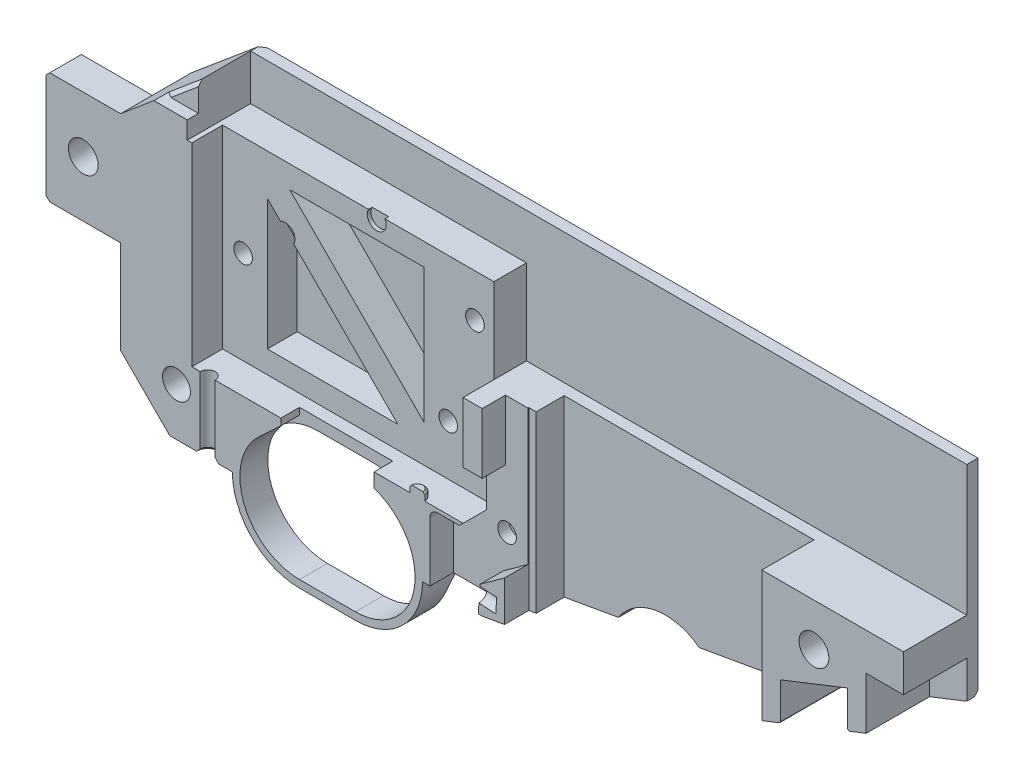
SolidWorks part; units mm, degrees
ref_plane "정면" through (0, 0, 0) normal (0, 0, 1) x (1, 0, 0)
ref_plane "윗면" through (0, 0, 0) normal (0, 1, 0) x (1, 0, 0)
ref_plane "우측면" through (0, 0, 0) normal (1, 0, 0) x (0, 0, -1)
sketch "스케치1" plane through (0, 0, 0) normal (0, 0, 1) x (1, 0, 0)
  line L0 (0, 0) -> (20, 0)
  line L1 (20, 0) -> (37.8763, 15)
  line L2 (37.8763, 15) -> (230, 15)
  line L3 (230, 15) -> (230, -54.9955)
  line L4 (230, -54.9955) -> (192, -54.9955)
  line L5 (0, 0) -> (0, -30)
  line L6 (0, -30) -> (20, -30)
  line L7 (20, -30) -> (20, -55)
  line L8 (20, -55) -> (33.22, -68.22)
  line L9 (33.22, -68.22) -> (50, -68.22)
  line L10 (68, -68.22) -> (83, -68.22) construction
  line L11 (68, -52.22) -> (83, -52.22)
  line L12 (68, -84.22) -> (83, -84.22)
  line L13 (67.2987, -49.22) -> (82.2987, -49.22)
  line L14 (139.5521, -64.2435) -> (117, -68.22)
  line L15 (101, -68.22) -> (117, -68.22)
  line L16 (117, -68.22) -> (192, -54.9955) construction
  line L17 (68, -86.22) -> (83, -86.22)
  line L18 (161.2179, -60.4232) -> (192, -54.9955)
  line L20 (68, -50.22) -> (83, -50.22) construction
  arc A0 (68, -52.22) -> (68, -84.22) centre (68, -68.22) ccw
  arc A1 (83, -84.22) -> (83, -52.22) centre (83, -68.22) ccw
  arc A3 (68, -50.22) -> (68, -86.22) centre (68, -68.22) ccw construction
  arc A4 (83, -86.22) -> (101, -68.22) centre (83, -68.22) ccw
  arc A5 (83, -86.22) -> (83, -50.22) centre (83, -68.22) ccw construction
  arc A6 (161.2179, -60.4232) -> (139.5521, -64.2435) centre (152.1559, -72.3764) ccw
  arc A7 (50, -68.22) -> (68, -86.22) centre (68, -68.22) ccw
  point P14 (75.5, -68.22)
  point P19 (80.5569, -40.2571)
  point P20 (93.5569, -40.2571)
  point P21 (93.5569, -59.2571)
  point P22 (93.5569, -78.2571)
  point P23 (80.5569, -78.2571)
  point P24 (80.5569, -59.2571)
  point P25 (50, -68.22)
  point P26 (101, -68.22)
  point P39 (139.5521, -64.2435)
  point P40 (161.2179, -60.4232)
  dimension "D4" = 16
  dimension "D13" = 16
  dimension "D14" = 15
  dimension "D1" = 230
  dimension "D2" = 30
  dimension "D3" = 15
  dimension "D6" = 2
  dimension "D5" = 16
  dimension "D7" = 3
  dimension "D8" = 135
  dimension "D9" = 64.22
  dimension "D10" = 140
  dimension "D11" = 170
  dimension "D12" = 15
  dimension "D15" = 30
  dimension "D16" = 75
  dimension "D17" = 51
  dimension "D18" = 22
  dimension "D19" = 20
  dimension "D20" = 25
  dimension "D21" = 22.9
  dimension "D22" = 20
extrude "보스-돌출1" add sketch "스케치1" along normal blind 20 contours L9 A7 L17 A4 L15 L16 L4 L3 L2 L1 L0 L5 L6 L7 L8 A1 L12 A0 L11 region at (119.6066, -23.0148, 0)
sketch "스케치2" plane through (0, 0, 20) normal (0, 0, 1) x (1, 0, 0)
  line L0 (68, -52.22) -> (83, -52.22) construction
  line L1 (39.125, 2.78) -> (111.875, 2.78)
  line L2 (39.125, 2.78) -> (39.125, -49.22)
  line L3 (39.125, -49.22) -> (111.875, -49.22)
  line L4 (111.875, 2.78) -> (111.875, -49.22)
  line L5 (75.5, -52.22) -> (75.5, -49.22) construction
  point P6 (75.5, -52.22)
  point P9 (75.5, -49.22)
  dimension "D1" = 52
  dimension "D2" = 72.75
  dimension "D3" = 3
extrude "컷-돌출1" cut sketch "스케치2" against normal blind 8.25
sketch "스케치3" plane through (0, 0, 20) normal (0, 0, 1) x (1, 0, 0)
  line L1 (37.8763, 2.78) -> (37.8763, 15)
  line L2 (37.8763, 15) -> (211, 15)
  line L5 (37.8763, 2.78) -> (211, 2.78)
  line L6 (211, 15) -> (211, 2.78)
  line L8 (211, -54.9955) -> (211, 15) construction
  line L9 (230, -54.9955) -> (192, -54.9955) construction
  line L10 (37.8763, 15) -> (230, 15) construction
  dimension "D1" = 12.22
extrude "컷-돌출4" cut sketch "스케치3" against normal blind 17
sketch "스케치5" plane through (0, 0, 20) normal (0, 0, 1) x (1, 0, 0)
  line L0 (192, -54.9955) -> (161.2179, -60.4232)
  line L1 (117, 2.0108) -> (192, 2.0088)
  line L2 (117, 2.0108) -> (117, -68.22)
  line L4 (192, 2.0088) -> (192, -54.9955)
  line L5 (161.2179, -60.4232) -> (192, -54.9955) construction
  line L6 (117, -68.22) -> (139.5521, -64.2435)
  arc A0 (139.5521, -64.2435) -> (161.2179, -60.4232) centre (152.1559, -72.3764) cw
extrude "컷-돌출5" cut sketch "스케치5" against normal blind 14
sketch "스케치6" plane through (0, 0, 20) normal (0, 0, 1) x (1, 0, 0)
  line L1 (63, -49.22) -> (88, -49.22)
  line L2 (39.125, -49.22) -> (111.875, -49.22) construction
  line L3 (68, -52.22) -> (83, -52.22)
  line L4 (88, -49.22) -> (88, -53.0213)
  line L5 (63, -49.22) -> (63, -53.0213)
  arc A0 (68, -52.22) -> (68, -84.22) centre (68, -68.22) ccw construction
  arc A1 (83, -84.22) -> (83, -52.22) centre (83, -68.22) ccw construction
  arc A2 (68, -52.22) -> (63, -53.0213) centre (68, -68.22) ccw
  arc A3 (88, -53.0213) -> (83, -52.22) centre (83, -68.22) ccw
  point P2 (75.5, -49.22)
  dimension "D1" = 25
extrude "컷-돌출6" cut sketch "스케치6" against normal blind 5
sketch "스케치7" plane through (0, -86.22, 0) normal (0, -1, 0) x (1, 0, 0)
  line L0 (75.5, 12.5) -> (93.5, 12.5)
  line L3 (75.5, 0) -> (101, 0)
  line L4 (75.5, 12.5) -> (50, 12.5)
  line L5 (75.5, 0) -> (75.5, 12.5)
  line L8 (50, 12.5) -> (50, 0)
  line L9 (93.5, 12.5) -> (101, 12.5)
  line L11 (101, 12.5) -> (101, 0)
  line L12 (50, 0) -> (75.5, 0)
  line M6 (68, 0) -> (83, 0)
  line M7 (83, 0) -> (83, 20)
  line M9 (68, 20) -> (68, 0)
  dimension "D1" = 12.5
extrude "컷-돌출7" cut sketch "스케치7" against normal up to surface (18 mm away) contours L5 L0 M6 M7 | L11 L9 L0 L3 M7 region at (79.25, -86.22, 6.25) region at (92, -86.22, 6.25) up to face at (110.6, -68.22, 9.2)
sketch "스케치11" plane through (0, 0, 0) normal (0, 0, -1) x (-1, 0, 0)
  line L0 (-50, -68.22) -> (-50, -42.5)
  line L1 (-50, -42.5) -> (-20, -42.5)
  line L2 (-20, -30) -> (-20, -55) construction
  line L3 (-20, -42.5) -> (-20, -55)
  line L4 (-20, -55) -> (-33.22, -68.22)
  line L5 (-33.22, -68.22) -> (-50, -68.22)
extrude "컷-돌출13" cut sketch "스케치11" against normal blind 8
sketch "스케치12" plane through (0, 0, 8) normal (0, 0, -1) x (-1, 0, 0)
  line L0 (-41.61, -68.22) -> (-41.61, -55.36)
  line L1 (-50, -68.22) -> (-33.22, -68.22) construction
  line L2 (-41.61, -55.36) -> (-50, -55.36)
  line L3 (-50, -42.5) -> (-50, -68.22) construction
  line L4 (-50, -55.36) -> (-50, -68.22)
  line L5 (-50, -68.22) -> (-41.61, -68.22)
extrude "컷-돌출15" cut sketch "스케치7<4>" against normal up to vertex (30.86 mm away) contours L5 L4 M6 M9 | L8 L12 L4 M9 region at (71.75, -86.22, 6.25) region at (59, -86.22, 6.25) up to point (50, -55.36, 8)
sketch "스케치7<4>" plane through (0, -86.22, 0) normal (0, -1, 0) x (1, 0, 0) same geometry as "스케치7"
fillet "필렛3" radius 7.5 1 edges at (54.2403, -55.36, 12.5) second distance 9 first distance on face at (72.5955, -74.4968, 12.5)
extrude "컷-돌출16" cut sketch "스케치12" against normal blind 6 contours L2 L4 L5 L0
chamfer "모따기4" distance 1 angle 45 1 edges at (41.61, -68.22, 11)
fillet "필렛4" radius 6 1 edges at (100, -68.22, 12.5) second distance 8 first distance on face at (107.2857, -68.22, 10.1429)
sketch "스케치13" plane through (0, 0, 20) normal (0, 0, 1) x (1, 0, 0)
  line L1 (230, 15) -> (111.87, 15)
  line L2 (230, 15) -> (230, -20)
  line L3 (230, -20) -> (111.87, -20)
  line L4 (111.87, 15) -> (111.87, -20)
  dimension "D1" = 35
  dimension "D2" = 118.13
extrude "컷-돌출17" cut sketch "스케치13" against normal blind 17
sketch "스케치14" plane through (0, 0, 20) normal (0, 0, 1) x (1, 0, 0)
  line L1 (230, -54.9955) -> (220, -54.9955)
  line L2 (230, -54.9955) -> (230, -29.9955)
  line L3 (230, -29.9955) -> (220, -29.9955)
  line L4 (220, -54.9955) -> (220, -29.9955)
  dimension "D1" = 10
  dimension "D2" = 25
extrude "컷-돌출18" cut sketch "스케치14" against normal blind 17
sketch "스케치16" plane through (0, 0, 0) normal (0, 0, -1) x (-1, 0, 0)
  line L0 (-192, -54.9955) -> (-230, -39.9955)
  line L1 (-230, 15) -> (-230, -54.9955) construction
  line L2 (-230, -39.9955) -> (-230, -54.9955)
  line L3 (-230, -54.9955) -> (-192, -54.9955)
  dimension "D1" = 15
extrude "컷-돌출19" cut sketch "스케치16" against normal up to next
sketch "스케치19" plane through (0, 0, 20) normal (0, 0, 1) x (1, 0, 0)
  line L1 (117, -20) -> (117, -68.22) construction
  line L2 (101, -68.22) -> (117, -68.22) construction
  line L3 (113, -68.22) -> (103, -68.22)
  line L4 (103, -68.22) -> (103, -50.22)
  line L6 (103, -50.22) -> (111.875, -50.22)
  line L7 (111.875, -50.22) -> (111.875, -36.22)
  line L8 (111.875, -49.22) -> (111.875, -20) construction
  line L9 (111.875, -36.22) -> (117, -36.22)
  line L10 (117, -36.22) -> (117, -64.22)
  line L11 (117, -64.22) -> (117, -68.22)
  line L12 (117, -68.22) -> (113, -68.22)
  dimension "D1" = 4
  dimension "D3" = 10
  dimension "D4" = 18
  dimension "D5" = 14
extrude "컷-돌출21" cut sketch "스케치19" against normal blind 6.25
fillet "필렛5" radius 2 1 edges at (103, -50.22, 16.875)
sketch "스케치21" plane through (0, 0, 8) normal (0, 0, -1) x (-1, 0, 0)
  line L0 (-50, -68.22) -> (-20, -42.5) construction
  circle A0 centre (-35, -55.36) radius 3.75
  dimension "D1" = 7.5
extrude "컷-돌출23" cut sketch "스케치21" against normal up to next
chamfer "모따기5" distance 1 angle 45 1 edges at (111.875, -50.22, 16.875)
sketch "스케치22" plane through (117, 0, 0) normal (1, 0, 0) x (0, 0, -1)
  line L0 (-13.5, -33.22) -> (-13.5, -68.22)
  line L2 (-13.75, -68.22) -> (-6, -68.22) construction
  line L3 (-13.5, -33.22) -> (-20, -33.22)
  line L4 (-20, -33.22) -> (-20, -68.22)
  line L5 (-20, -68.22) -> (-14, -68.22) construction
  line L6 (-20, -68.22) -> (-20, -86.22) construction
  line L7 (-13.5, -68.22) -> (-20, -68.22)
  dimension "D1" = 6.5
  dimension "D2" = 35
sketch "스케치24" plane through (0, 0, 0) normal (0, 0, -1) x (-1, 0, 0)
  line L1 (0, 0) -> (-20, 0)
  line L2 (0, 0) -> (0, -30)
  line L3 (0, -30) -> (-20, -30)
  line L4 (-20, 0) -> (-20, -30)
extrude "컷-돌출26" cut sketch "스케치24" against normal blind 11.5
sketch "스케치25" plane through (0, 0, 0) normal (0, 0, -1) x (-1, 0, 0)
  line L0 (-117, -68.22) -> (-117, -13.2245)
  line L1 (-189, -28.0267) -> (-120, -40.1933)
  line L2 (-192, 0) -> (-192, -54.9955)
  line L3 (-139.5521, -64.2435) -> (-117, -68.22) construction
  line L4 (-161.2179, -60.4232) -> (-192, -54.9955) construction
  line L5 (-161.2179, -60.4232) -> (-192, -54.9955)
  line L6 (-139.5521, -64.2435) -> (-117, -68.22)
  line L7 (-120, -64.6447) -> (-120, -15.7418)
  line L8 (-189, -3.5753) -> (-120, -15.7418)
  line L9 (-189, -3.5753) -> (-189, -52.4782)
  line L10 (-161.9179, -57.2535) -> (-189, -52.4782)
  line L11 (-137.8102, -61.5043) -> (-120, -64.6447)
  line L12 (-192, 0) -> (-117, -13.2245)
  line L13 (-189, -3) -> (-189, -52.4782) construction
  line L14 (-120, -64.6447) -> (-120, -3) construction
  line L15 (-117, -68.22) -> (-117, 0) construction
  line L16 (-120, -3) -> (-189, -3) construction
  line L17 (-117, 0) -> (-192, 0) construction
  line L18 (-189, -30.9811) -> (-120, -43.1477)
  line L19 (-189, -25.0723) -> (-120, -37.2389)
  line L20 (-189, -28.0267) -> (-194.8846, -26.9891)
  line L21 (-120, -40.1933) -> (-111.0757, -41.7669)
  line L22 (-120, -15.7418) -> (-189, -15.7418)
  arc A0 (-139.5521, -64.2435) -> (-161.2179, -60.4232) centre (-152.1559, -72.3764) ccw construction
  arc A1 (-139.5521, -64.2435) -> (-161.2179, -60.4232) centre (-152.1559, -72.3764) ccw
  arc A2 (-137.8102, -61.5043) -> (-161.9179, -57.2535) centre (-152.1559, -72.3764) ccw
  point P17 (-192.5209, -2.9544)
  point P18 (-117.5209, -16.1789)
  dimension "D1" = 3
extrude "컷-돌출27" cut sketch "스케치25" against normal blind 2 contours A2 L11 L7 L9 L10 | L9 L19 L7 L8 region at (154.7863, -47.2575, 0) region at (149.9613, -23.8488, 0)
fillet "필렛6" radius 1 19 edges at (128.9051, -63.0745, 0) (128.9051, -63.0745, 2) (149.0302, -54.6499, 0) (149.0302, -54.6499, 2) (175.4589, -54.8658, 0) (175.4589, -54.8658, 2) (189, -41.7297, 0) (189, -41.7297, 2) (120, -53.8962, 0) (120, -53.8962, 2) (154.5, -37.0644, 0) (154.5, -31.1556, 0) (189, -20.4071, 2) (120, -26.4903, 2) (154.5, -31.1556, 2) (154.5, -37.0644, 2) (189, -20.4071, 0) (154.5, -15.7418, 0) (154.5, -15.7418, 2)
sketch "스케치29" plane through (37.8763, 0, 0) normal (1, 0, 0) x (0, 0, -1)
  line L1 (-20, 15) -> (-17, 15)
  line L2 (-20, 15) -> (-20, 7.5)
  line L3 (-20, 7.5) -> (-17, 7.5)
  line L4 (-17, 15) -> (-17, 7.5)
  dimension "D1" = 3
  dimension "D2" = 7.5
extrude "컷-돌출28" cut sketch "스케치29" against normal blind 10
chamfer "모따기6" distance 1 angle 45 1 edges at (33.4072, 11.25, 17)
sketch "스케치30" plane through (0, -68.22, 0) normal (0, -1, 0) x (1, 0, 0)
  line L0 (33.22, 20) -> (50, 20) construction
  circle A0 centre (43.375, 20) radius 2
  dimension "D2" = 4
  dimension "D1" = 6.625
extrude "컷-돌출29" cut sketch "스케치30" against normal through all
chamfer "모따기7" distance 1 angle 45 1 edges at (43.375, -68.22, 18)
sketch "스케치31" plane through (0, -49.22, 0) normal (0, 1, 0) x (1, 0, 0)
  line L0 (88, -20) -> (111.875, -20) construction
  line L1 (101.6, -20) -> (97.65, -20)
  arc A0 (101.6, -20) -> (97.65, -20) centre (99.625, -20) ccw
  dimension "D2" = 3.95
  dimension "D1" = 12.25
extrude "보스-돌출3" add sketch "스케치31" along normal blind 2
chamfer "모따기8" distance 0.5 angle 45 1 edges at (99.625, -47.22, 18.025)
sketch "스케치32" plane through (0, 0, 11.5) normal (0, 0, -1) x (-1, 0, 0)
  line L0 (0, 0) -> (-20, -30) construction
  circle A0 centre (-10, -15) radius 4
  dimension "D1" = 8
extrude "컷-돌출30" cut sketch "스케치32" against normal through all
sketch "스케치33" plane through (0, 0, 11.75) normal (0, 0, 1) x (1, 0, 0)
  line L0 (111.875, -36.22) -> (111.875, -49.22) construction
  line L1 (39.125, -49.22) -> (111.875, -49.22) construction
  circle A0 centre (99.637, -35.72) radius 2.5
  dimension "D1" = 5
  dimension "D2" = 12.238
  dimension "D3" = 13.5
extrude "컷-돌출31" cut sketch "스케치33" against normal up to next
sketch "스케치35" plane through (0, 0, 11.75) normal (0, 0, 1) x (1, 0, 0)
  line L0 (39.125, 2.78) -> (39.125, -49.22) construction
  line L1 (39.125, -49.22) -> (111.875, -49.22) construction
  circle A0 centre (44.625, -24.22) radius 2.5
  dimension "D1" = 5
  dimension "D2" = 5.5
  dimension "D3" = 25
extrude "컷-돌출33" cut sketch "스케치35" against normal up to next
sketch "스케치36" plane through (0, 0, 11.75) normal (0, 0, 1) x (1, 0, 0)
  line L0 (39.125, -49.22) -> (111.875, -49.22) construction
  line L1 (111.87, 2.78) -> (111.87, -20) construction
  circle A0 centre (106.817, -8.72) radius 2.5
  dimension "D3" = 5
  dimension "D1" = 40.5
  dimension "D2" = 5.053
extrude "컷-돌출34" cut sketch "스케치36" against normal up to next
sketch "스케치38" plane through (0, 0, 0) normal (0, 0, -1) x (-1, 0, 0)
  circle A0 centre (-106.817, -8.72) radius 4
  circle A1 centre (-99.637, -35.72) radius 4
  circle A2 centre (-44.625, -24.22) radius 4
  circle A3 centre (-106.817, -8.72) radius 2.5
  circle A4 centre (-99.637, -35.72) radius 2.5
  circle A5 centre (-44.625, -24.22) radius 2.5
  dimension "D1" = 8
  dimension "D2" = 8
  dimension "D3" = 8
extrude "컷-돌출35" cut sketch "스케치38" against normal blind 4
sketch "스케치39" plane through (0, 0, 11.75) normal (0, 0, 1) x (1, 0, 0)
  line L0 (39.125, -49.22) -> (111.875, -49.22) construction
  line L1 (51.125, -3.22) -> (93.125, -3.22)
  line L2 (51.125, -3.22) -> (51.125, -43.22)
  line L3 (51.125, -43.22) -> (93.125, -43.22)
  line L4 (93.125, -3.22) -> (93.125, -43.22)
  line L5 (39.125, 2.78) -> (39.125, -49.22) construction
  line L6 (51.125, -8.22) -> (86.125, -43.22)
  line L7 (57.125, -3.22) -> (93.125, -39.22)
  dimension "D1" = 6
  dimension "D2" = 12
  dimension "D3" = 42
  dimension "D4" = 45
  dimension "D5" = 45
  dimension "D6" = 40
  dimension "D7" = 4
  dimension "D8" = 35
extrude "컷-돌출37" cut sketch "스케치39" against normal blind 8 contours L6 L2 L3 | L1 L7 L4 region at (81.125, -15.22, 11.75) region at (62.7917, -31.5533, 11.75)
chamfer "모따기10" distance 1 angle 45 10 edges at (54.2403, -55.36, 0) (62.988, -53.0253, 0) (75.5, -52.22, 0) (94.3137, -56.9063, 0) (108, -68.22, 0) (128.276, -66.2317, 0) (149.5511, -57.6043, 0) (176.6089, -57.7093, 0) (211, -47.4955, 0) (28.9382, 7.5, 0)
chamfer "모따기11" distance 2 angle 47 1 edges at (63, -53.0213, 17.5) first distance on face at (63, -51.1207, 17.5)
sketch "스케치40" plane through (0, 0, 11.75) normal (0, 0, 1) x (1, 0, 0)
  line L0 (39.125, 2.78) -> (39.125, -49.22) construction
  line L1 (39.125, -49.22) -> (111.875, -49.22) construction
  line L2 (111.87, 2.78) -> (111.87, -20) construction
  line L3 (111.87, 2.78) -> (39.125, 2.78) construction
  circle A0 centre (55.976, -14.01) radius 2.55
  circle A1 centre (80.467, 1.49) radius 2.55
  dimension "D1" = 5.1
  dimension "D6" = 5.1
  dimension "D2" = 16.851
  dimension "D3" = 35.21
  dimension "D4" = 31.403
  dimension "D5" = 1.29
extrude "컷-돌출38" cut sketch "스케치40" against normal blind 1
sketch "스케치42" plane through (0, 0, 0) normal (0, 0, -1) x (-1, 0, 0)
  line L0 (-111.87, -20) -> (-230, -20) construction
  line L1 (-215, -25) -> (-197, -25)
  line L2 (-215, -25) -> (-215, -63.3849)
  line L3 (-215, -63.3849) -> (-197, -63.3849)
  line L4 (-197, -25) -> (-197, -63.3849)
  line L5 (-192, -54.9955) -> (-192, -20) construction
  dimension "D1" = 5
  dimension "D2" = 5
  dimension "D3" = 18
extrude "컷-돌출39" cut sketch "스케치42" against normal blind 12
sketch "스케치45" plane through (0, 0, 12) normal (0, 0, -1) x (-1, 0, 0)
  line L0 (-215, -35.9165) -> (-197, -43.0218)
  line L1 (-215, -25) -> (-215, -45.9165) construction
  line L2 (-197, -53.0218) -> (-197, -25) construction
  line L3 (-215, -45.9165) -> (-197, -53.0218) construction
  line L4 (-197, -43.0218) -> (-197, -53.0218)
  line L5 (-197, -53.0218) -> (-215, -45.9165)
  line L6 (-215, -45.9165) -> (-215, -35.9165)
  dimension "D1" = 10
extrude "컷-돌출43" cut sketch "스케치45" against normal up to next
fillet "필렛8" radius 0.5 2 edges at (197, -53.0218, 10.5) (215, -45.9165, 10.5)
sketch "스케치47" plane through (0, 0, 12) normal (0, 0, -1) x (-1, 0, 0)
  line L0 (-215, -27.9165) -> (-197, -35.0218) construction
  line L1 (-215, -25) -> (-215, -35.9165) construction
  line L2 (-197, -43.0218) -> (-197, -25) construction
  line L3 (-197, -43.0218) -> (-215, -35.9165) construction
  circle A0 centre (-206, -31.4692) radius 4
  dimension "D2" = 8
  dimension "D1" = 8
extrude "컷-돌출44" cut sketch "스케치47" against normal up to next
fillet "필렛9" radius 1 1 edges at (202, -31.4692, 12)
sketch "스케치48" plane through (0, 0, 6) normal (0, 0, 1) x (1, 0, 0)
  line L0 (125, -66.8094) -> (117, -68.22)
  line L1 (117, -68.22) -> (139.5521, -64.2435) construction
  line L2 (117, -68.22) -> (117, -20)
  line L3 (117, -20) -> (125, -20)
  line L4 (192, -20) -> (117, -20) construction
  line L5 (125, -20) -> (125, -66.8094)
  dimension "D1" = 8
extrude "보스-돌출4" add sketch "스케치48" along normal up to surface (7.75 mm away) up to face at (109.9013, -51.2932, 13.75)
sketch "스케치50" plane through (125, 0, 0) normal (1, 0, 0) x (0, 0, -1)
  line L2 (-13.5, -68.22) -> (-20, -68.22) construction
  line L3 (-13.5, -20) -> (-13.5, -68.22)
  line L4 (-20, -20) -> (-20, -68.22)
  line L5 (-13.5, -68.22) -> (-20, -68.22)
  line L6 (-13.75, -20) -> (-6, -20) construction
  line L7 (-13.5, -20) -> (-20, -20)
extrude "컷-돌출45" cut sketch "스케치50" against normal blind 2
sketch "스케치51" plane through (0, 0, 13.75) normal (0, 0, 1) x (1, 0, 0)
  line L0 (123, -67.162) -> (111.875, -36.22) construction
  line L1 (111.875, -36.22) -> (111.875, -49.22) construction
  line L2 (117, -36.22) -> (111.875, -36.22) construction
  circle A0 centre (117.4375, -51.691) radius 2.5
  dimension "D1" = 5
extrude "컷-돌출46" cut sketch "스케치51" against normal blind 3
sketch "스케치52" plane through (0, 0, 10.75) normal (0, 0, 1) x (1, 0, 0)
  circle A0 centre (117.4375, -51.691) radius 1.1
  dimension "D1" = 2.2
extrude "컷-돌출47" cut sketch "스케치52" against normal through all
sketch "스케치53" plane through (0, 0, 13.75) normal (0, 0, 1) x (1, 0, 0)
  line L0 (123, -67.162) -> (123, -56.362)
  line L1 (123, -20) -> (123, -67.162) construction
  line L2 (123, -56.362) -> (116.4479, -61.1)
  line L3 (116.4479, -61.1) -> (115.95, -68.22)
  line L4 (103, -68.22) -> (117, -68.22) construction
  line L5 (115.95, -68.22) -> (117, -68.22)
  line L6 (117, -68.22) -> (123, -67.162)
  dimension "D1" = 10.8
  dimension "D2" = 1.05
  dimension "D3" = 86
  dimension "D4" = 7.12
extrude "보스-돌출5" add sketch "스케치53" along normal up to surface (6.25 mm away) up to face at (14, -15, 20)
sketch "스케치54" plane through (120.133, -8.4005, 0) normal (-0.9976, 0.0698, 0) x (0, 0, 1)
  circle A0 centre (20, -55.3282) radius 2
  dimension "D1" = 4
  dimension "D2" = 2.5
extrude "컷-돌출48" cut sketch "스케치54" against normal blind 4.5
chamfer "모따기12" distance 1 angle 45 3 edges at (0, -30, 15.75) (0, -15, 11.5) (0, 0, 15.75)
